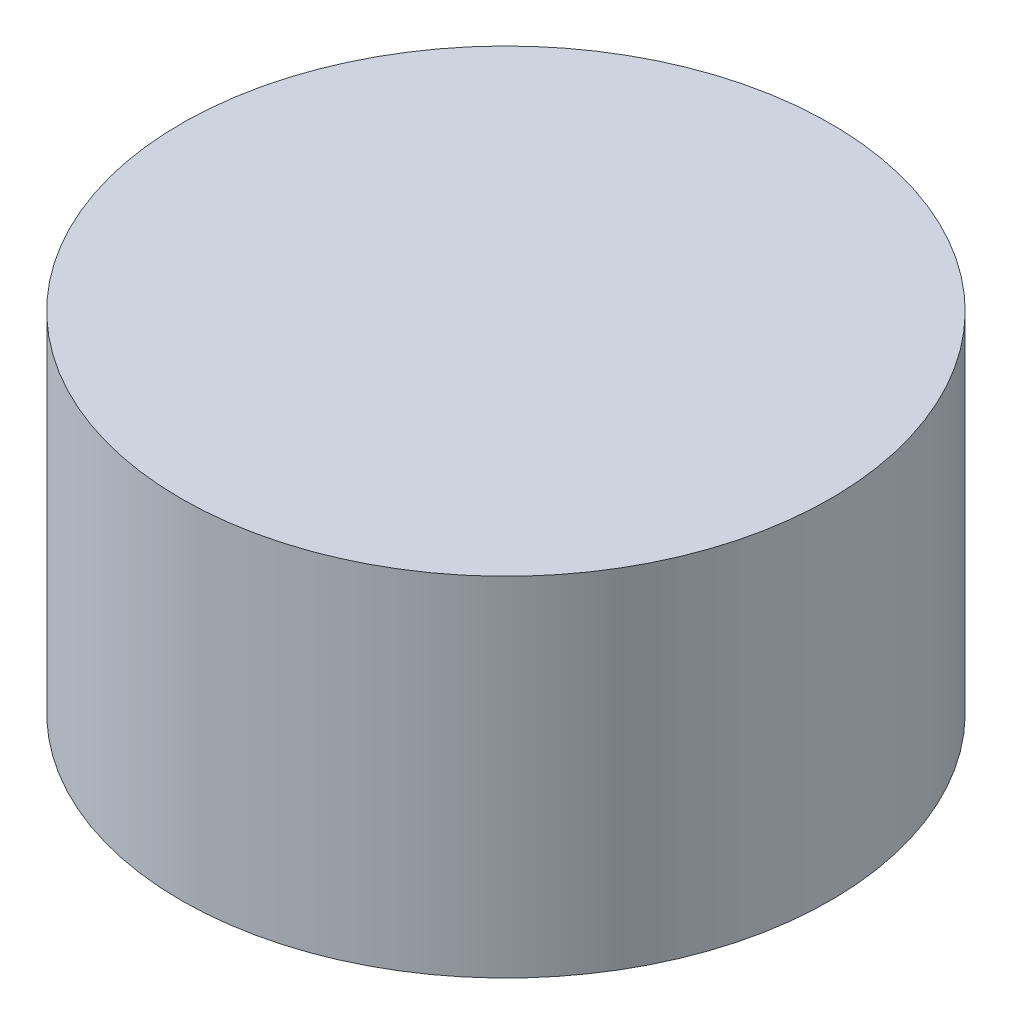
SolidWorks part; units mm, degrees
ref_plane "前视基准面" through (0, 0, 0) normal (0, 0, 1) x (1, 0, 0)
ref_plane "上视基准面" through (0, 0, 0) normal (0, 1, 0) x (1, 0, 0)
ref_plane "右视基准面" through (0, 0, 0) normal (1, 0, 0) x (0, 0, -1)
other "Configuration Table"
sketch "草图1" plane through (0, 0, 0) normal (0, 1, 0) x (1, 0, 0)
  circle A0 centre (0, 0) radius 5.6
  dimension "D2" = 11.2
extrude "凸台-拉伸1" add sketch "草图1" along normal blind 6 contours A0
